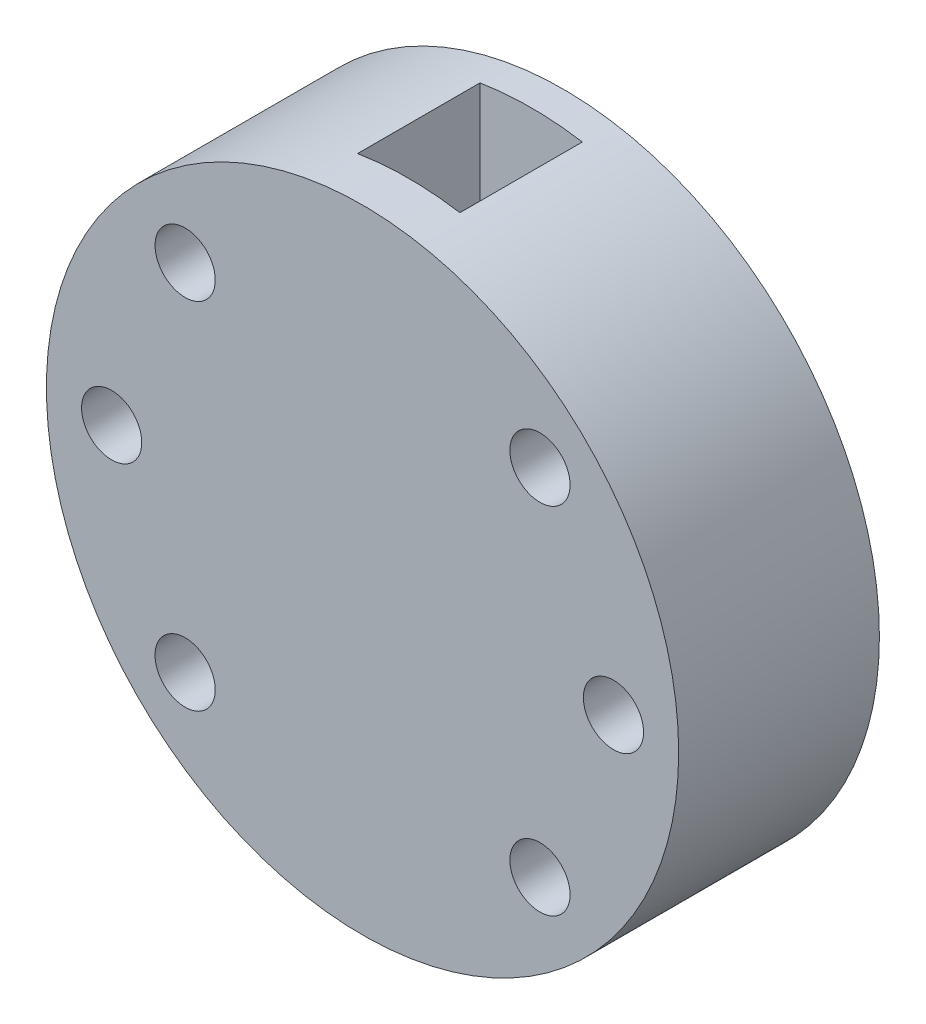
SolidWorks part; units mm, degrees
ref_plane "Front Plane" through (0, 0, 0) normal (0, 0, 1) x (1, 0, 0)
ref_plane "Top Plane" through (0, 0, 0) normal (0, 1, 0) x (1, 0, 0)
ref_plane "Right Plane" through (0, 0, 0) normal (1, 0, 0) x (0, 0, -1)
sketch "Sketch2" plane through (0, 0, 0) normal (0, 0, 1) x (1, 0, 0)
  line L0 (0, 25) -> (0, -25) construction
  line L1 (-25, 0) -> (25, 0) construction
  line L2 (17.6777, 17.6777) -> (-17.6777, -17.6777) construction
  line L3 (-17.6777, 17.6777) -> (17.6777, -17.6777) construction
  circle A0 centre (0, 0) radius 31.5
  circle A1 centre (0, 0) radius 25
  circle A2 centre (-17.6777, 17.6777) radius 3
  circle A3 centre (-25, 0) radius 3
  circle A4 centre (-17.6777, -17.6777) radius 3
  circle A5 centre (17.6777, 17.6777) radius 3
  circle A6 centre (25, 0) radius 3
  circle A7 centre (17.6777, -17.6777) radius 3
  circle A8 centre (-17.6777, 17.6777) radius 4.5
  circle A9 centre (-25, 0) radius 4.5
  circle A10 centre (-17.6777, -17.6777) radius 4.5
  circle A11 centre (17.6777, 17.6777) radius 4.5
  circle A12 centre (25, 0) radius 4.5
  circle A13 centre (17.6777, -17.6777) radius 4.5
extrude "Boss-Extrude2" add sketch "Sketch2" along normal blind 20 contours A0 A13 A1 A10 A9 A8 A11 A12 | A13 A1 A12 A11 A8 A9 A10 region at (-30.609, 0, 0) region at (0, 0, 0)
ref_plane "Plane1" through (0, 32.2538, 0) normal (0, 1, 0) x (1, 0, 0)
sketch "Sketch3" plane through (0, 32.2538, 0) normal (0, 1, 0) x (1, 0, 0)
  line L0 (0, 0) -> (0, -10.0485) construction
  line L1 (-5.1, -3.2) -> (5.1, -3.2)
  line L2 (17.6777, 0) -> (-17.6777, 0) construction
  line L3 (5.1, -3.2) -> (5.1, -15.4)
  line L4 (5.1, -15.4) -> (-5.1, -15.4)
  line L5 (-5.1, -15.4) -> (-5.1, -3.2)
  point P6 (0, -3.2)
  dimension "D1" = 3.2
  dimension "D2" = 10.2
  dimension "D3" = 12.2
extrude "Cut-Extrude1" cut sketch "Sketch3" against normal blind 80 and the other way blind 26
extrude "Boss-Extrude3" add sketch "Sketch2<4>" along normal blind 20 contours A9 | A10 | A13 | A12 | A11 | A8
sketch "Sketch2<4>" plane through (0, 0, 0) normal (0, 0, 1) x (1, 0, 0) same geometry as "Sketch2"
extrude "Cut-Extrude2" cut sketch "Sketch2<5>" along normal blind 6 contours A9 | A10 | A8 | A13 | A12 | A11
sketch "Sketch2<5>" plane through (0, 0, 0) normal (0, 0, 1) x (1, 0, 0) same geometry as "Sketch2"
extrude "Cut-Extrude3" cut sketch "Sketch2<6>" along normal blind 20 contours A2 | A3 | A4 | A7 | A6 | A5
sketch "Sketch2<6>" plane through (0, 0, 0) normal (0, 0, 1) x (1, 0, 0) same geometry as "Sketch2"
